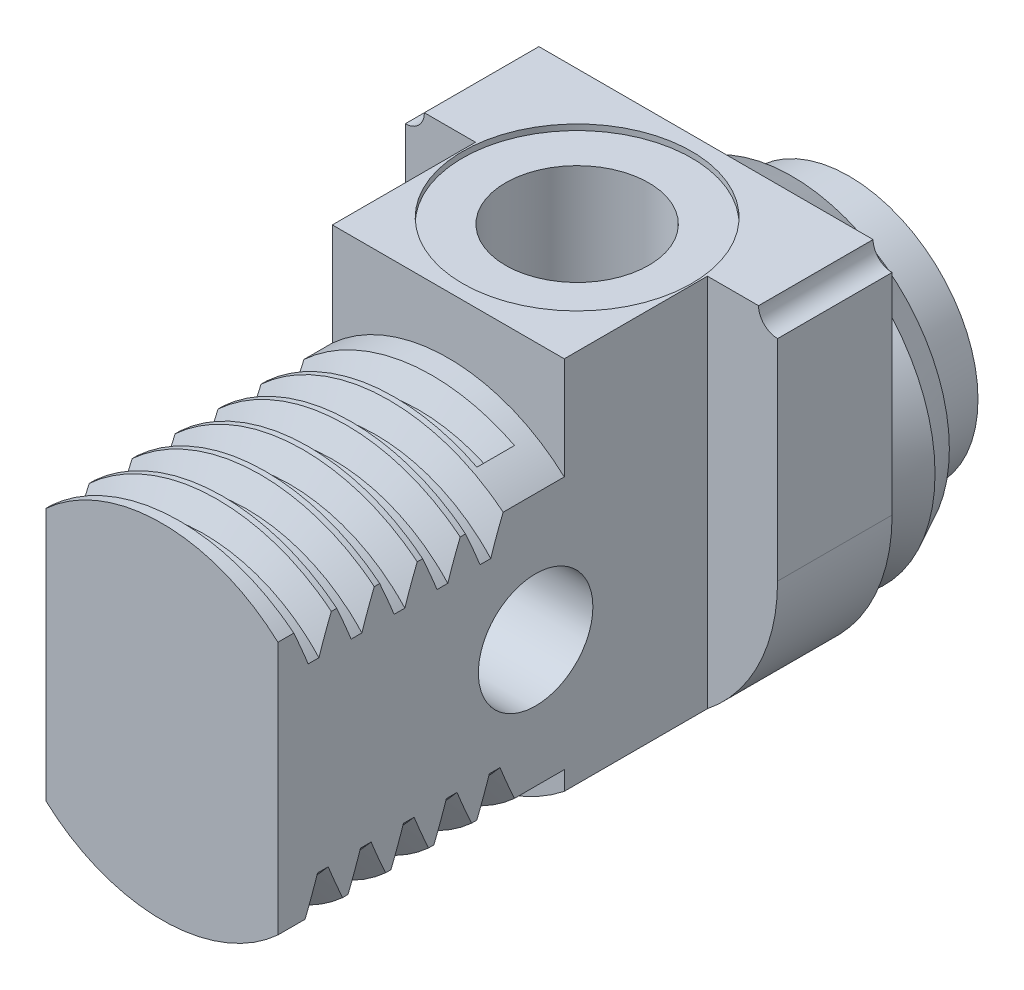
SolidWorks part; units mm, degrees
ref_plane "Front Plane" through (0, 0, 0) normal (0, 0, 1) x (1, 0, 0)
ref_plane "Top Plane" through (0, 0, 0) normal (0, 1, 0) x (1, 0, 0)
ref_plane "Right Plane" through (0, 0, 0) normal (1, 0, 0) x (0, 0, -1)
sketch "Sketch1" plane through (0, 0, 0) normal (0, 0, 1) x (1, 0, 0)
  circle A0 centre (0, 0) radius 5.5
  dimension "D1" = 11
ref_plane "Plane1" through (0, 0, 1) normal (0, 0, 1) x (1, 0, 0)
sketch "Sketch2" plane through (0, 0, 1) normal (0, 0, 1) x (1, 0, 0)
  circle A0 centre (0, 0) radius 6
  dimension "D1" = 12
ref_plane "Plane2" through (0, 0, 3) normal (0, 0, 1) x (1, 0, 0)
sketch "Sketch3" plane through (0, 0, 3) normal (0, 0, 1) x (1, 0, 0)
  circle A0 centre (0, 0) radius 5
  dimension "D1" = 10
loft "Loft1" add profiles "Sketch1", "Sketch2"
sketch "Sketch4" plane through (0, 0, 1) normal (0, 0, 1) x (1, 0, 0)
  circle A0 centre (0, 0) radius 6
loft "Loft3" add profiles "Sketch4", "Sketch3"
sketch "Sketch5" plane through (0, 0, 3) normal (0, 0, 1) x (1, 0, 0)
  circle A1 centre (0, 0) radius 6.5
  dimension "D1" = 13
extrude "Boss-Extrude1" add sketch "Sketch5" along normal blind 9
ref_plane "Plane3" through (0, 8, 0) normal (0, 1, 0) x (1, 0, 0)
sketch "Sketch6" plane through (0, 8, 0) normal (0, 1, 0) x (1, 0, 0)
  line L1 (-6.5, -3) -> (6.5, -3)
  line L2 (-6.5, -3) -> (-6.5, -12)
  line L3 (-6.5, -12) -> (6.5, -12)
  line L4 (6.5, -3) -> (6.5, -12)
extrude "Boss-Extrude2" add sketch "Sketch6" against normal up to surface (8 mm away) up to face at (6.5, 0, 12)
sketch "Sketch7" plane through (0, 0, 3) normal (0, 0, -1) x (-1, 0, 0)
  line L0 (-6.5, 8) -> (6.5, 8) construction
  line L1 (-6.5, 0) -> (-6.5, 8) construction
  line L2 (6.5, 0) -> (6.5, 8) construction
  line L3 (-6.5, 8) -> (-5.836, 8)
  line L4 (-6.5, 7.336) -> (-6.5, 8)
  line L5 (5.836, 8) -> (6.5, 8)
  line L6 (6.5, 7.336) -> (6.5, 8)
  arc A0 (-5.836, 8) -> (-6.5, 7.336) centre (-6.5, 8) cw
  arc A1 (6.5, 7.336) -> (5.836, 8) centre (6.5, 8) cw
extrude "Cut-Extrude1" cut sketch "Sketch7" against normal blind 9
sketch "Sketch8" plane through (0, 0, 12) normal (0, 0, 1) x (1, 0, 0)
  circle A0 centre (0, 0) radius 6
  dimension "D1" = 12
extrude "Boss-Extrude3" add sketch "Sketch8" along normal blind 10
thread "Thread1" pitch 1.5 start angle 0, offset 0, length 0, pitch 1.5, diameter 12
ref_plane "Plane4" through (-6, 0, 22) normal (0, -1, 0) x (-1, 0, 0)
sketch "Thread Profile1" plane through (-6, 0, 22) normal (0, -1, 0) x (-1, 0, 0)
  line L0 (0, 0) -> (0, 1.5) construction
  line L11 (0, 0) -> (0, 1.3125)
  line L12 (0, 1.3125) -> (-0.8119, 0.8437)
  line L13 (-0.8119, 0.8437) -> (-0.8119, 0.4687)
  line L15 (-0.8119, 0.4687) -> (0, 0)
  line L17 (-0.8119, 0.6562) -> (0, 0.6562) construction
  point P2 (0, 0)
  dimension "Pitch" = 1.5
  dimension "Profile_Angle" = 60
  dimension "Profile_Land" = 0.375
  dimension "Profile_Height" = 0.8119
sketch "Sketch16" plane through (0, 8, 0) normal (0, 1, 0) x (1, 0, 0)
  line L0 (5, -3) -> (-5, -3) construction
  circle A0 centre (0, -7.5) radius 4
  point P2 (0, 0)
  dimension "D1" = 8
  dimension "D2" = 4.5
extrude "Cut-Extrude4" cut sketch "Sketch16" against normal blind 0.2
sketch "Sketch17" plane through (0, 7.8, 0) normal (0, 1, 0) x (1, 0, 0)
  circle A0 centre (0, -7.5) radius 2.5
  dimension "D1" = 5
extrude "Cut-Extrude7" cut sketch "Sketch17" against normal blind 10
sketch "Sketch19" plane through (0, 8, 0) normal (0, 1, 0) x (1, 0, 0)
  line L1 (-6.5, -7) -> (-4.05, -7)
  line L2 (-6.5, -7) -> (-6.5, -22.7994)
  line L3 (-6.5, -22.7994) -> (-4.05, -22.7994)
  line L4 (-4.05, -7) -> (-4.05, -22.7994)
  line L5 (6.5, -7) -> (4.05, -7)
  line L6 (6.5, -7) -> (6.5, -22.7994)
  line L7 (6.5, -22.7994) -> (4.05, -22.7994)
  line L8 (4.05, -7) -> (4.05, -22.7994)
  line L11 (5.836, -3) -> (-5.836, -3) construction
  line L14 (-6.5, -12) -> (-6.5, -3) construction
  line L15 (6.5, -12) -> (6.5, -3) construction
  circle A7 centre (0, -7.5) radius 4 construction
  dimension "D1" = 4
  dimension "D2" = 4.05
  dimension "D3" = 4.05
extrude "Cut-Extrude18" cut sketch "Sketch19" against normal up to next
sketch "Sketch20" plane through (4.05, 0, 0) normal (1, 0, 0) x (0, 0, -1)
  line L0 (-22, -4.4269) -> (-22, 4.4269) construction
  circle A0 centre (-13, 0) radius 2
  dimension "D1" = 4
  dimension "D2" = 9
extrude "Cut-Extrude19" cut sketch "Sketch20" against normal up to next
sketch "Sketch21" plane through (0, 0, 0) normal (0, 0, -1) x (-1, 0, 0)
  circle A0 centre (0, 0) radius 4.5
  dimension "D1" = 9
extrude "Boss-Extrude4" add sketch "Sketch21" along normal blind 2
